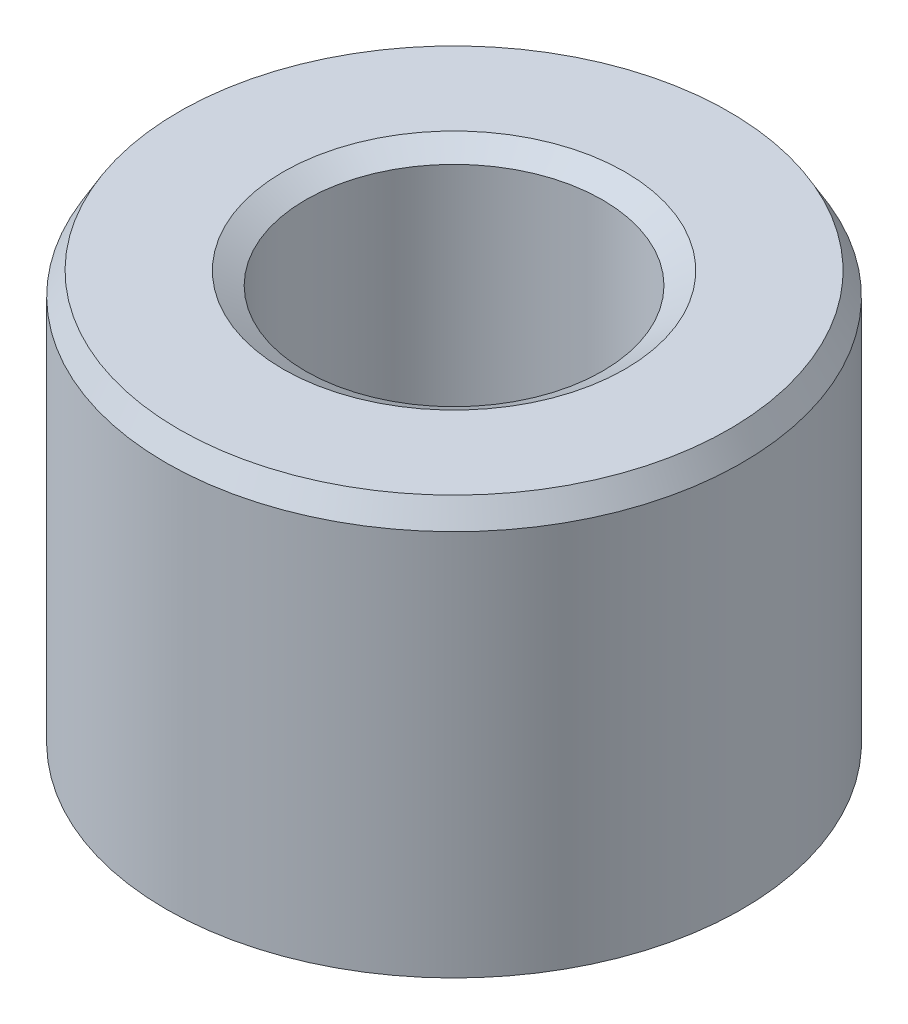
SolidWorks part; units mm, degrees
ref_plane "Front Plane" through (0, 0, 0) normal (0, 0, 1) x (1, 0, 0)
ref_plane "Top Plane" through (0, 0, 0) normal (0, 1, 0) x (1, 0, 0)
ref_plane "Right Plane" through (0, 0, 0) normal (1, 0, 0) x (0, 0, -1)
sketch "Sketch1" plane through (0, 0, 0) normal (0, 1, 0) x (1, 0, 0)
  circle A0 centre (0, 0) radius 37.5
  dimension "SLEEVE_OD" = 75
extrude "Boss-Extrude1" add sketch "Sketch1" along normal blind 54.9305
sketch "Sketch2" plane through (0, 0, 0) normal (0, 1, 0) x (1, 0, 0)
  circle A0 centre (0, 0) radius 19.3232
  dimension "BORE_D" = 38.6463
extrude "Cut-Extrude1" cut sketch "Sketch2" along normal through all
chamfer "Chamfer1" distance 2.9267 angle 30 4 edges at (0, 54.9305, 19.3232) (0, 0, 19.3232) (0, 0, 37.5) (0, 54.9305, 37.5) first distance on face at (0, 54.9305, 19.3232) first distance on face at (0, 0, 19.3232) first distance on face at (0, 54.9305, 37.5)
